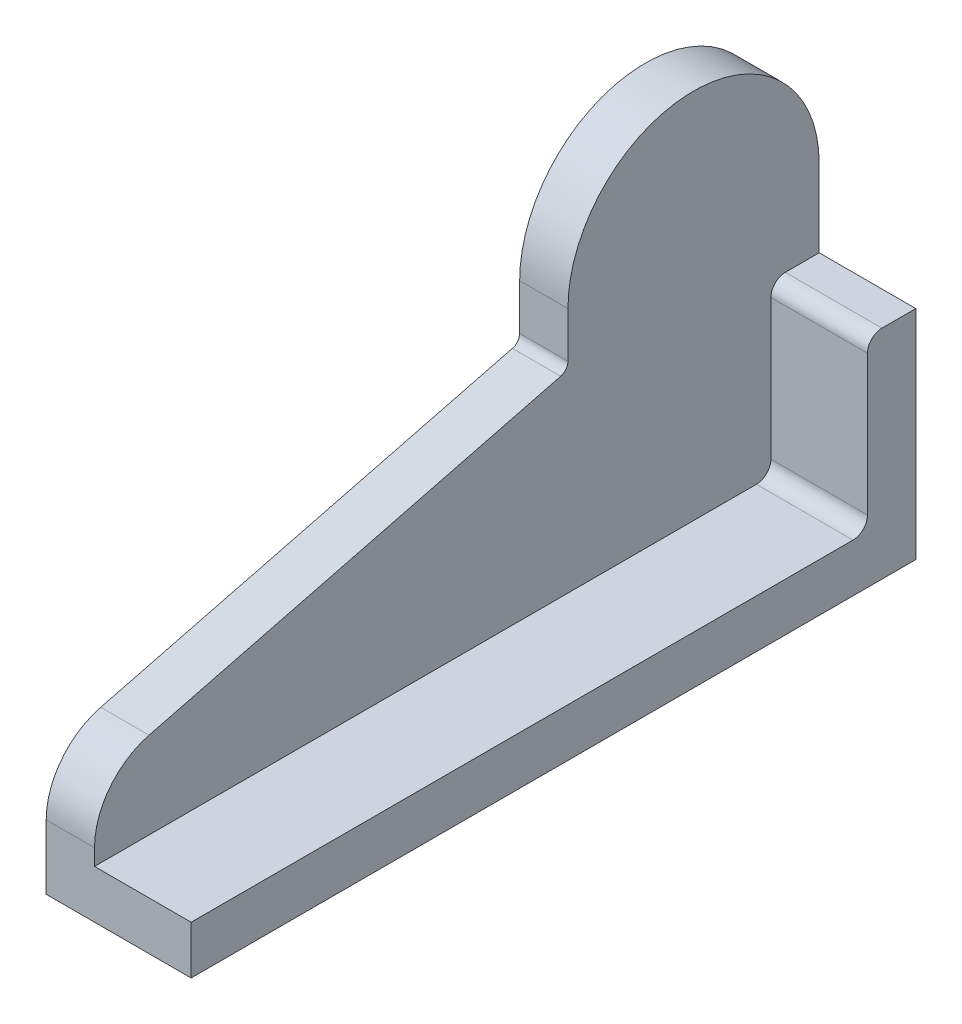
SolidWorks part; units mm, degrees
ref_plane "Front Plane" through (0, 0, 0) normal (0, 0, 1) x (1, 0, 0)
ref_plane "Top Plane" through (0, 0, 0) normal (0, 1, 0) x (1, 0, 0)
ref_plane "Right Plane" through (0, 0, 0) normal (1, 0, 0) x (0, 0, -1)
sketch "Sketch1" plane through (0, 0, 0) normal (0, 1, 0) x (1, 0, 0)
  line L1 (-41, -75) -> (41, -75)
  line L2 (-41, -75) -> (-41, 75)
  line L3 (-41, 75) -> (41, 75)
  line L4 (41, -75) -> (41, 75)
  line L5 (-41, -75) -> (41, 75) construction
  line L6 (-41, 75) -> (41, -75) construction
  point P0 (0, 0)
  dimension "D1" = 82
  dimension "D2" = 150
extrude "Boss-Extrude1" add sketch "Sketch1" along normal blind 10
sketch "Sketch2" plane through (41, 0, 0) normal (1, 0, 0) x (0, 0, -1)
  line L1 (75, 0) -> (65, 0)
  line L2 (75, 0) -> (75, 45)
  line L3 (75, 45) -> (65, 45)
  line L4 (65, 0) -> (65, 45)
  dimension "D1" = 10
  dimension "D2" = 45
extrude "Boss-Extrude2" add sketch "Sketch2" against normal through all
sketch "Sketch3" plane through (0, 0, -65) normal (0, 0, 1) x (1, 0, 0)
  line L0 (-41, 45) -> (41, 45) construction
  line L2 (10, 45) -> (10, 10)
  line L3 (10, 10) -> (20, 10)
  line L4 (20, 45) -> (20, 10)
  line L5 (-41, 10) -> (41, 10) construction
  line L6 (41, 45) -> (41, 10) construction
  line L7 (0, -55) -> (0, 55) construction
  line L9 (10, 45) -> (10, 87)
  line L10 (10, 87) -> (20, 87)
  line L11 (20, 45) -> (20, 87)
  line L12 (-10, 45) -> (-10, 87)
  line L13 (-10, 87) -> (-20, 87)
  line L14 (-20, 45) -> (-20, 87)
  line L15 (-20, 45) -> (-20, 10)
  line L16 (-10, 10) -> (-20, 10)
  line L17 (-10, 45) -> (-10, 10)
  dimension "D1" = 21
  dimension "D2" = 10
  dimension "D3" = 42
extrude "Boss-Extrude3" add sketch "Sketch3" along normal blind 42 and the other way blind 10
fillet "Fillet3" 2 edges at (15, 87, -23) (15, 87, -75) type full round first side face at (15, 48.5, -23) second side face at (0, 51.5, -75) middle face at (15, 87, -49)
fillet "Fillet4" 2 edges at (-15, 87, -23) (-15, 87, -75) type full round first side face at (-15, 48.5, -23) second side face at (0, 47.1667, -75) middle face at (-15, 87, -49)
sketch "Sketch4" plane through (20, 0, 0) normal (1, 0, 0) x (0, 0, -1)
  line L0 (23, 10) -> (23, 50)
  line L1 (23, 10) -> (23, 61) construction
  line L2 (23, 50) -> (-75, 25)
  line L3 (-75, 25) -> (-75, 10)
  line L4 (-75, 10) -> (23, 10)
  dimension "D1" = 15
  dimension "D2" = 40
extrude "Boss-Extrude4" add sketch "Sketch4" against normal up to surface (10 mm away) up to face at (10, 43, -54.3333)
sketch "Sketch5" plane through (-20, 0, 0) normal (-1, 0, 0) x (0, 0, 1)
  line L0 (-23, 50) -> (75, 25)
  line L1 (75, 25) -> (75, 10)
  line L2 (75, 10) -> (-23, 10)
  line L3 (-23, 10) -> (-23, 50)
extrude "Boss-Extrude5" add sketch "Sketch5" against normal up to surface (10 mm away) up to face at (-10, 43, -54.3333)
fillet "Fillet5" radius 15 1 edges at (15, 25, 75)
fillet "Fillet6" radius 15 1 edges at (-15, 25, 75)
sketch "Sketch6" plane through (20, 0, 0) normal (1, 0, 0) x (0, 0, -1)
  line L0 (65, 10) -> (-75, 10) construction
  line L1 (-75, 10) -> (-75, 0) construction
  circle A0 centre (49, 61) radius 8
  circle A1 centre (-60, 17.5) radius 5.5
  dimension "D1" = 7.5
  dimension "D3" = 11
  dimension "D2" = 15
extrude "Cut-Extrude1" cut sketch "Sketch6" against normal through all
fillet "Fillet7" radius 3 1 edges at (30.5, 45, -65)
fillet "Fillet8" radius 3 1 edges at (0, 45, -65)
fillet "Fillet9" radius 3 1 edges at (-30.5, 45, -65)
fillet "Fillet10" radius 3 3 edges at (-30.5, 10, -65) (0, 10, -65) (30.5, 10, -65)
fillet "Fillet11" radius 2 2 edges at (-15, 50, -23) (15, 50, -23)
sketch "Sketch7" plane through (0, 10, 0) normal (0, 1, 0) x (1, 0, 0)
  line L0 (20, 75) -> (41, 75) construction
  line L1 (20, 62) -> (20, -75) construction
  line L3 (20, 21.4944) -> (20, -63.7078) construction
  line L4 (0, -55) -> (0, 55) construction
  circle A0 centre (31.5, 45) radius 5.5
  circle A1 centre (31.5, -15) radius 5.5
  circle A2 centre (-31.5, -15) radius 5.5
  circle A3 centre (-31.5, 45) radius 5.5
  dimension "D1" = 30
  dimension "D3" = 11
  dimension "D4" = 11.5
  dimension "D6" = 11
  dimension "D2" = 11.5
  dimension "D5" = 60
extrude "Cut-Extrude2" cut sketch "Sketch7" against normal through all
ref_plane "Plane1" through (10, 0, 0) normal (-1, 0, 0) x (0, 0, 1)
ref_plane "Plane2" through (-20, 0, 0) normal (-1, 0, 0) x (0, 0, 1)
sketch "Sketch8" plane through (10, 0, 0) normal (-1, 0, 0) x (0, 0, 1)
  line L1 (-94.2601, 100.0064) -> (94.4464, 100.0064)
  line L2 (-94.2601, 100.0064) -> (-94.2601, -8.5976)
  line L3 (-94.2601, -8.5976) -> (94.4464, -8.5976)
  line L4 (94.4464, 100.0064) -> (94.4464, -8.5976)
extrude "Cut-Extrude3" cut sketch "Sketch8" against normal through all
sketch "Sketch9" plane through (-20, 0, 0) normal (-1, 0, 0) x (0, 0, 1)
  line L1 (-92.2702, 92.5083) -> (96.5321, 92.5083)
  line L2 (-92.2702, 92.5083) -> (-92.2702, -22.7762)
  line L3 (-92.2702, -22.7762) -> (96.5321, -22.7762)
  line L4 (96.5321, 92.5083) -> (96.5321, -22.7762)
extrude "Cut-Extrude4" cut sketch "Sketch9" along normal through all
sketch "Sketch10" plane through (-20, 0, 0) normal (-1, 0, 0) x (0, 0, 1)
  line L1 (-60.9659, 70.7653) -> (-36.7489, 70.7653)
  line L2 (-60.9659, 70.7653) -> (-60.9659, 50.1046)
  line L3 (-60.9659, 50.1046) -> (-36.7489, 50.1046)
  line L4 (-36.7489, 70.7653) -> (-36.7489, 50.1046)
  line L5 (53.6839, 23.6861) -> (67.4012, 23.6861)
  line L6 (53.6839, 23.6861) -> (53.6839, 10.3074)
  line L7 (53.6839, 10.3074) -> (67.4012, 10.3074)
  line L8 (67.4012, 23.6861) -> (67.4012, 10.3074)
extrude "Boss-Extrude6" add sketch "Sketch10" against normal blind 10
